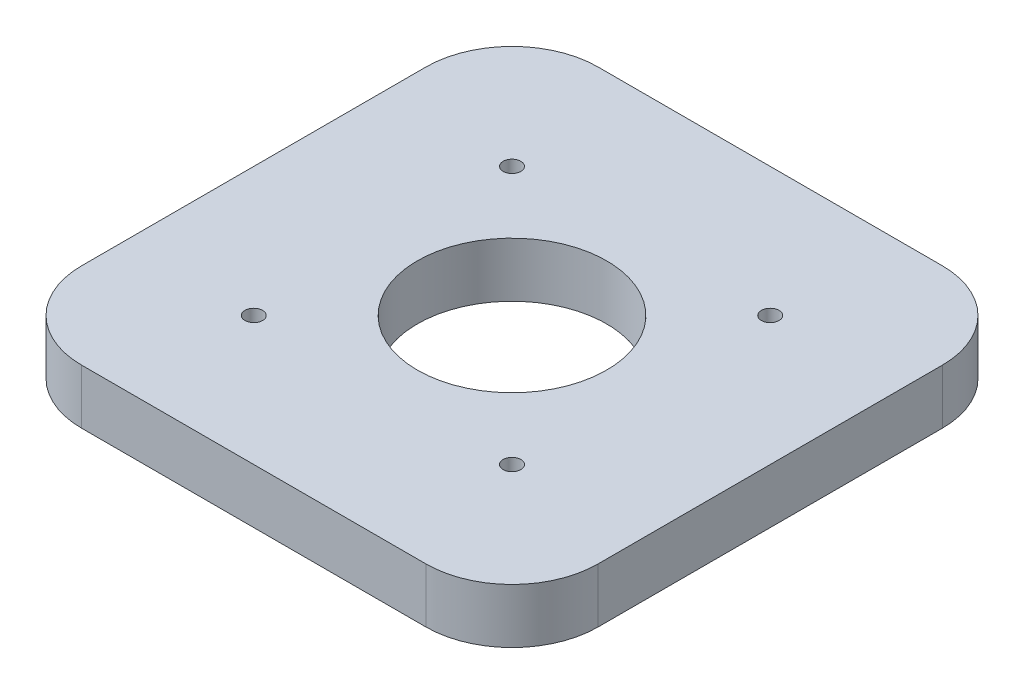
SolidWorks part; units mm, degrees
material "Oak"
ref_plane "Front Plane" through (0, 0, 0) normal (0, 0, 1) x (1, 0, 0)
ref_plane "Top Plane" through (0, 0, 0) normal (0, 1, 0) x (1, 0, 0)
ref_plane "Right Plane" through (0, 0, 0) normal (1, 0, 0) x (0, 0, -1)
sketch "Sketch3" plane through (0, 0, 0) normal (0, 1, 0) x (1, 0, 0)
  line L1 (40, -46.6704) -> (100, -46.6704)
  line L2 (40, -46.6704) -> (40, -106.6704)
  line L3 (40, -106.6704) -> (100, -106.6704)
  line L4 (100, -46.6704) -> (100, -106.6704)
  line L5 (70, -76.6704) -> (85, -76.6704) construction
  line L6 (70, -76.6704) -> (70, -91.6704) construction
  line L7 (70, -91.6704) -> (85, -91.6704) construction
  line L8 (85, -76.6704) -> (85, -91.6704) construction
  line L9 (55, -61.6704) -> (85, -61.6704) construction
  line L10 (55, -61.6704) -> (55, -91.6704) construction
  line L11 (55, -91.6704) -> (85, -91.6704) construction
  line L12 (85, -61.6704) -> (85, -91.6704) construction
  line L13 (55, -61.6704) -> (85, -91.6704) construction
  line L14 (55, -91.6704) -> (85, -61.6704) construction
  circle A0 centre (70, -76.6704) radius 11
  circle A1 centre (55, -61.6704) radius 1.025
  circle A2 centre (85, -61.6704) radius 1.025
  circle A3 centre (85, -91.6704) radius 1.025
  circle A4 centre (55, -91.6704) radius 1.025
  dimension "D5" = 22
  dimension "D8" = 2.05
  dimension "D9" = 2.05
  dimension "D10" = 2.05
  dimension "D11" = 2.05
  dimension "D1" = 60
  dimension "D2" = 60
  dimension "D3" = 30
  dimension "D4" = 30
  dimension "D6" = 15
  dimension "D7" = 15
extrude "Boss-Extrude1" add sketch "Sketch3" along normal blind 6.35
fillet "Fillet1" radius 10 4 edges at (100, 3.175, 106.6704) (100, 3.175, 46.6704) (40, 3.175, 46.6704) (40, 3.175, 106.6704)
